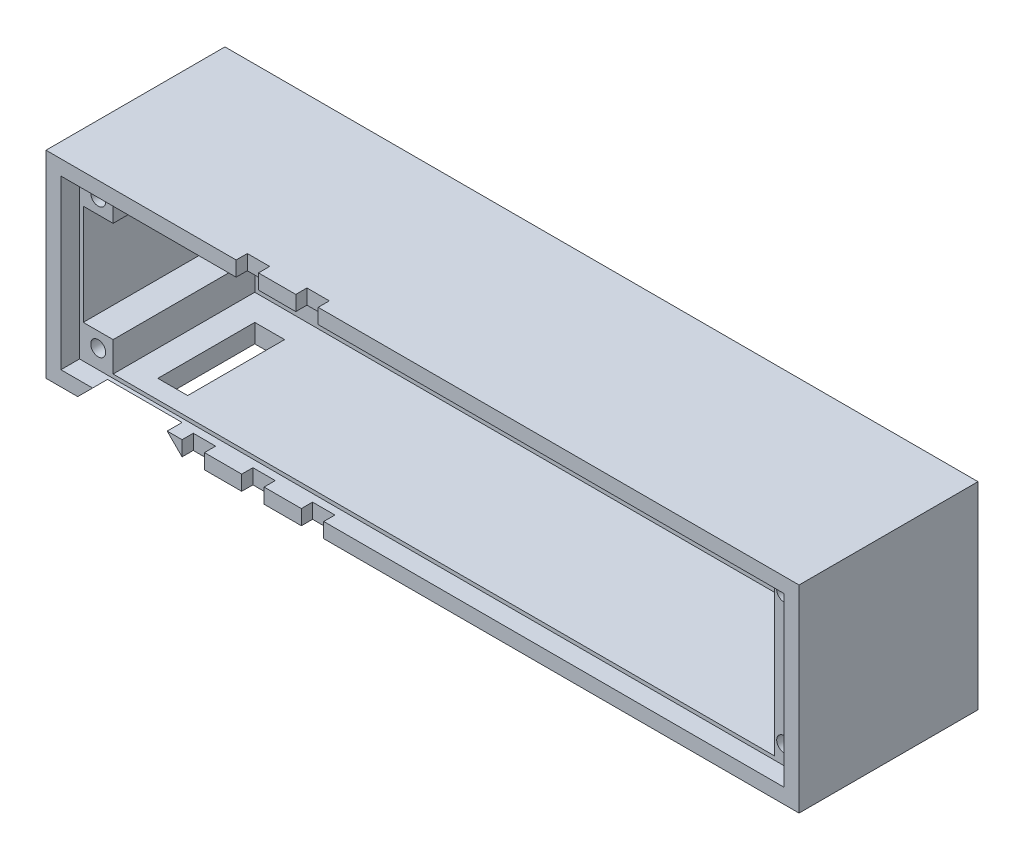
SolidWorks part; units mm, degrees
ref_plane "前视基准面" through (0, 0, 0) normal (0, 0, 1) x (1, 0, 0)
ref_plane "上视基准面" through (0, 0, 0) normal (0, 1, 0) x (1, 0, 0)
ref_plane "右视基准面" through (0, 0, 0) normal (1, 0, 0) x (0, 0, -1)
other "Configuration Table"
sketch "草图1" plane through (0, 0, 0) normal (0, 0, 1) x (1, 0, 0)
  line L1 (0, 0) -> (101, 0)
  line L2 (0, 0) -> (0, 26.5)
  line L3 (0, 26.5) -> (101, 26.5)
  line L4 (101, 0) -> (101, 26.5)
  dimension "D1" = 101
  dimension "D2" = 26.5
extrude "凸台-拉伸1" add sketch "草图1" along normal blind 2.5
sketch "草图2" plane through (0, 0, 2.5) normal (0, 0, 1) x (1, 0, 0)
  line L0 (98.5, 24) -> (2.5, 24)
  line L1 (2.5, 24) -> (2.5, 2.5)
  line L2 (2.5, 2.5) -> (98.5, 2.5)
  line L3 (98.5, 2.5) -> (98.5, 24)
  line L4 (0, 26.5) -> (0, 0)
  line L5 (0, 0) -> (101, 0)
  line L6 (101, 0) -> (101, 26.5)
  line L7 (101, 26.5) -> (0, 26.5)
  line L8 (0, 26.5) -> (0, 0)
  line L9 (0, 0) -> (101, 0)
  line L10 (101, 0) -> (101, 26.5)
  line L11 (101, 26.5) -> (0, 26.5)
  dimension "D1" = 0
  dimension "D2" = 2.5
extrude "凸台-拉伸2" add sketch "草图2" along normal blind 21.5
sketch "草图3" plane through (0, 0, 2.5) normal (0, 0, 1) x (1, 0, 0)
  line L1 (2.5, 24) -> (6.5, 24)
  line L2 (2.5, 24) -> (2.5, 20)
  line L4 (6.5, 24) -> (6.5, 20)
  line L5 (2.5, 2.5) -> (6.5, 2.5)
  line L6 (2.5, 2.5) -> (2.5, 6.5)
  line L8 (6.5, 2.5) -> (6.5, 6.5)
  line L9 (98.5, 24) -> (95.1958, 24)
  line L10 (98.5, 24) -> (98.5, 17.7456)
  line L12 (95.1958, 24) -> (95.1958, 20)
  line L13 (98.5, 2.5) -> (95.1958, 2.5)
  line L14 (98.5, 2.5) -> (98.5, 8.7544)
  line L16 (95.1958, 2.5) -> (95.1958, 6.5)
  line L21 (2.5, 20) -> (6.5, 20)
  line L23 (2.5, 6.5) -> (6.5, 6.5)
  line L26 (95.1958, 20) -> (95.1958, 6.5)
  line L28 (98.5, 17.7456) -> (98.5, 8.7544)
  dimension "D1" = 4
  dimension "D2" = 4
  dimension "D3" = 4
  dimension "D4" = 4
  dimension "D5" = 4
  dimension "D6" = 4
  dimension "D7" = 4
  dimension "D8" = 4
extrude "凸台-拉伸3" add sketch "草图3" along normal blind 19
sketch "草图5" plane through (0, 0, 21.5) normal (0, 0, 1) x (1, 0, 0)
  line L0 (2.5, 24) -> (6.5, 20) construction
  line L1 (6.5, 6.5) -> (2.5, 2.5) construction
  line L2 (98.5, 2.5) -> (98.5, 24) construction
  line L3 (98.5, 24) -> (95.1958, 24) construction
  line L10 (98.5, 2.5) -> (98.5, 24) construction
  circle A0 centre (4.5, 22) radius 1
  circle A1 centre (4.5, 4.5) radius 1
  circle A2 centre (96.5, 22) radius 1
  circle A3 centre (96.5, 4.5) radius 1
  dimension "D1" = 2
  dimension "D2" = 2
  dimension "D3" = 2
  dimension "D4" = 17.5
  dimension "D5" = 2
extrude "切除-拉伸1" cut sketch "草图5" against normal blind 12
sketch "草图6" plane through (0, 0, 0) normal (0, -1, 0) x (1, 0, 0)
  line L6 (0, 24) -> (0, 0) construction
  line L7 (10, 19) -> (43, 19)
  line L8 (10, 19) -> (10, 6)
  line L9 (10, 6) -> (43, 6)
  line L10 (43, 19) -> (43, 6)
  line L11 (0, 24) -> (101, 24) construction
  dimension "D1" = 13
  dimension "D2" = 33
  dimension "D3" = 10
  dimension "D4" = 5
extrude "切除-拉伸2" cut sketch "草图6" against normal blind 1.5
sketch "草图7" plane through (0, 1.5, 0) normal (0, -1, 0) x (1, 0, 0)
  line L0 (10, 6) -> (43, 6) construction
  line L1 (10, 19) -> (14, 19)
  line L2 (10, 19) -> (10, 6)
  line L3 (10, 6) -> (14, 6)
  line L4 (14, 19) -> (14, 6)
  dimension "D1" = 4
extrude "切除-拉伸3" cut sketch "草图7" against normal blind 1.5
sketch "草图8" plane through (0, 0, 24) normal (0, 0, 1) x (1, 0, 0)
  line L8 (99, 24.5) -> (2, 24.5)
  line L9 (2, 24.5) -> (2, 2)
  line L10 (2, 2) -> (99, 2)
  line L11 (99, 2) -> (99, 24.5)
  line L12 (99, 24.5) -> (2, 24.5)
  line L13 (2, 24.5) -> (2, 2)
  line L14 (2, 2) -> (99, 2)
  line L15 (99, 2) -> (99, 24.5)
  dimension "D1" = 2
extrude "切除-拉伸4" cut sketch "草图8" against normal up to surface (2.5 mm away) contours L12 L13 L14 L15 up to face at (5.5, 22, 21.5)
sketch "草图9" plane through (0, 0, 0) normal (0, -1, 0) x (1, 0, 0)
  line L0 (0, 24) -> (101, 24) construction
  line L1 (6.25, 24) -> (16.25, 24)
  line L2 (6.25, 24) -> (6.25, 22)
  line L3 (6.25, 22) -> (16.25, 22)
  line L4 (16.25, 24) -> (16.25, 22)
  line L5 (0, 24) -> (0, 0) construction
  line L7 (18.25, 24) -> (21.25, 24)
  line L8 (18.25, 24) -> (18.25, 22.5)
  line L9 (18.25, 22.5) -> (21.25, 22.5)
  line L10 (21.25, 24) -> (21.25, 22.5)
  line L11 (26.25, 24) -> (29.25, 24)
  line L12 (26.25, 24) -> (26.25, 22.5)
  line L13 (26.25, 22.5) -> (29.25, 22.5)
  line L14 (29.25, 24) -> (29.25, 22.5)
  line L15 (34.25, 24) -> (37.25, 24)
  line L16 (34.25, 24) -> (34.25, 22.5)
  line L17 (34.25, 22.5) -> (37.25, 22.5)
  line L18 (37.25, 24) -> (37.25, 22.5)
  dimension "D1" = 6.25
  dimension "D2" = 10
  dimension "D3" = 2
  dimension "D4" = 1.5
  dimension "D5" = 2
  dimension "D6" = 3
  dimension "D7" = 5
  dimension "D8" = 3
  dimension "D9" = 1.5
  dimension "D10" = 5
  dimension "D11" = 3
  dimension "D12" = 1.5
extrude "切除-拉伸5" cut sketch "草图9" against normal up to next
chamfer "倒角1" distance 2 angle 45 3 edges at (16.25, 0, 23) (11.25, 0, 22) (6.25, 0, 23)
sketch "草图11" plane through (0, 26.5, 0) normal (0, 1, 0) x (1, 0, 0)
  line L6 (101, -24) -> (0, -24) construction
  line L7 (28.5, -24) -> (25.5, -24)
  line L8 (28.5, -24) -> (28.5, -22.5)
  line L9 (28.5, -22.5) -> (25.5, -22.5)
  line L10 (25.5, -24) -> (25.5, -22.5)
  line L11 (0, -24) -> (0, 0) construction
  line L13 (33.5, -24) -> (36.5, -24)
  line L14 (33.5, -24) -> (33.5, -22.5)
  line L15 (33.5, -22.5) -> (36.5, -22.5)
  line L16 (36.5, -24) -> (36.5, -22.5)
  dimension "D1" = 25.5
  dimension "D2" = 1.5
  dimension "D3" = 3
  dimension "D4" = 3
  dimension "D5" = 5
  dimension "D6" = 1.5
extrude "切除-拉伸6" cut sketch "草图11" against normal up to next
sketch "草图12" plane through (0, 0, 0) normal (0, 0, -1) x (-1, 0, 0)
  line L1 (-6, 18.5) -> (-3, 18.5)
  line L2 (-6, 18.5) -> (-6, 15.5)
  line L3 (-6, 15.5) -> (-3, 15.5)
  line L4 (-3, 18.5) -> (-3, 15.5)
  line L6 (0, 26.5) -> (0, 0) construction
  line L7 (-101, 26.5) -> (0, 26.5) construction
  dimension "D1" = 3
  dimension "D2" = 8
  dimension "D3" = 3
  dimension "D4" = 3
extrude "切除-拉伸7" cut sketch "草图12" against normal up to next
sketch "草图14" plane through (0, 0, 2.5) normal (0, 0, 1) x (1, 0, 0)
  line L0 (6, 15.5) -> (6, 18.5) construction
  line L1 (2.5, 20) -> (6.5, 20)
  line L2 (2.5, 20) -> (2.5, 14.5)
  line L3 (2.5, 14.5) -> (6.5, 14.5)
  line L4 (6.5, 20) -> (6.5, 14.5)
  line L5 (3, 15.5) -> (6, 15.5) construction
  line L6 (3, 18.5) -> (3, 15.5) construction
  line L7 (6, 18.5) -> (3, 18.5) construction
  line L8 (6, 15.5) -> (6, 18.5)
  line L9 (3, 15.5) -> (6, 15.5)
  line L10 (3, 18.5) -> (3, 15.5)
  line L11 (6, 18.5) -> (3, 18.5)
  line L12 (6.5, 20) -> (6.5, 24) construction
  line M6 (3, 18.5) -> (6, 18.5)
  line M7 (6, 18.5) -> (6, 15.5)
  line M8 (6, 15.5) -> (3, 15.5)
  line M9 (3, 15.5) -> (3, 18.5)
  dimension "D1" = 0
  dimension "D2" = 1
extrude "凸台-拉伸4" add sketch "草图14" along normal blind 5 contours M6 M9 M8 M7 | L2 L1 L4 L3 region at (4.5, 17, 2.5)
sketch "草图13" plane through (0, 0, 0) normal (-1, 0, 0) x (0, 0, 1)
  line L0 (24, 26.5) -> (0, 26.5) construction
  line L1 (3, 18.5) -> (6, 18.5)
  line L2 (3, 18.5) -> (3, 15.5)
  line L3 (3, 15.5) -> (6, 15.5)
  line L4 (6, 18.5) -> (6, 15.5)
  line L5 (0, 26.5) -> (0, 0) construction
  dimension "D1" = 8
  dimension "D2" = 3
  dimension "D3" = 3
  dimension "D4" = 3
extrude "切除-拉伸8" cut sketch "草图13" against normal up to next
sketch "草图15" plane through (0, 0, 7.5) normal (0, 0, 1) x (1, 0, 0)
  line L4 (2.5, 14.5) -> (6.5, 14.5)
  line L5 (6.5, 14.5) -> (6.5, 20)
  line L6 (6.5, 20) -> (2.5, 20)
  line L7 (2.5, 20) -> (2.5, 14.5)
  line L8 (2.5, 14.5) -> (6.5, 14.5)
  line L9 (6.5, 14.5) -> (6.5, 20)
  line L10 (6.5, 20) -> (2.5, 20)
  line L11 (2.5, 20) -> (2.5, 14.5)
  dimension "D1" = 0
extrude "凸台-拉伸5" add sketch "草图15" against normal up to surface (1.5 mm away) up to face at (1.5, 17, 6)
